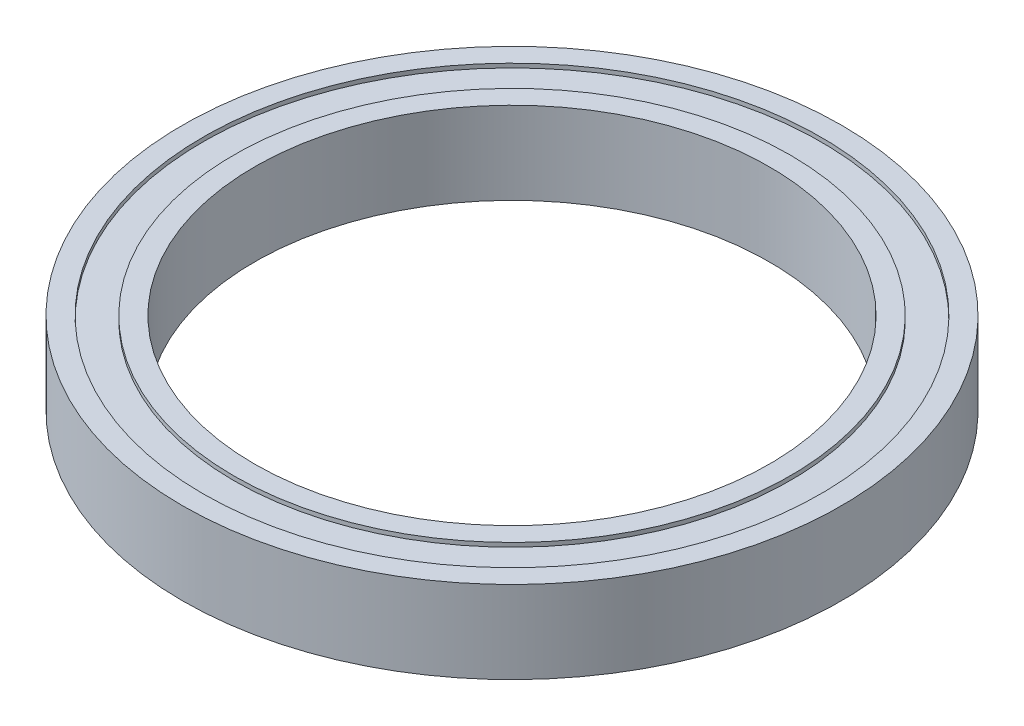
SolidWorks part; units mm, degrees
material "AISI 1035 Steel (SS)"
ref_plane "Front Plane" through (0, 0, 0) normal (0, 0, 1) x (1, 0, 0)
ref_plane "Top Plane" through (0, 0, 0) normal (0, 1, 0) x (1, 0, 0)
ref_plane "Right Plane" through (0, 0, 0) normal (1, 0, 0) x (0, 0, -1)
sketch "Sketch1" plane through (0, 0, 0) normal (0, 1, 0) x (1, 0, 0)
  circle A0 centre (0, 0) radius 16
  circle A1 centre (0, 0) radius 12.5
  dimension "D1" = 32
  dimension "D2" = 25
extrude "Boss-Extrude1" add sketch "Sketch1" along normal blind 4
sketch "Sketch2" plane through (0, 4, 0) normal (0, 1, 0) x (1, 0, 0)
  circle A0 centre (0, 0) radius 13.5
  circle A1 centre (0, 0) radius 15
  circle A2 centre (0, 0) radius 12.5 construction
  circle A3 centre (0, 0) radius 16 construction
  dimension "D1" = 1
  dimension "D2" = 1
extrude "Cut-Extrude1" cut sketch "Sketch2" against normal blind 0.2
sketch "Sketch3" plane through (0, 0, 0) normal (0, -1, 0) x (1, 0, 0)
  circle A0 centre (0, 0) radius 13.5
  circle A1 centre (0, 0) radius 15
  circle A2 centre (0, 0) radius 12.5 construction
  circle A3 centre (0, 0) radius 16 construction
  dimension "D1" = 1
  dimension "D2" = 1
extrude "Cut-Extrude2" cut sketch "Sketch3" against normal blind 0.2
sketch "Sketch4" plane through (0, 0, 0) normal (1, 0, 0) x (0, 0, -1)
  line L0 (0, 10.7298) -> (0, -9.2634) construction
  line L2 (13.7144, 3.4768) -> (15.7144, 3.4768)
  line L3 (13.7144, 3.4768) -> (13.7144, 1.4768)
  line L4 (13.7144, 1.4768) -> (15.7144, 1.4768)
  line L5 (15.7144, 3.4768) -> (15.7144, 1.4768)
  point P7 (0, 0)
  point P8 (0, 0)
  point P9 (0, 0)
  point P10 (0, 0)
  dimension "D1" = 2
  dimension "D2" = 2
revolve "Revolve1" add sketch "Sketch4" angle 360 about L0
